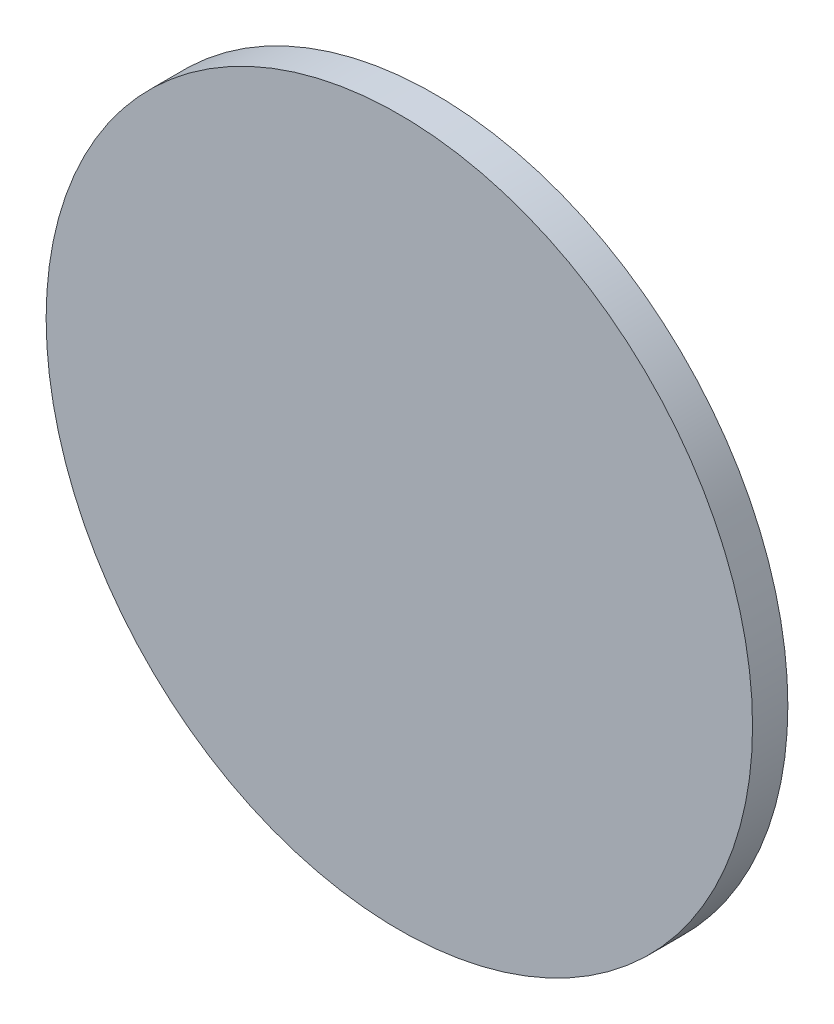
SolidWorks part; units mm, degrees
ref_plane "Front Plane" through (0, 0, 0) normal (0, 0, 1) x (1, 0, 0)
ref_plane "Top Plane" through (0, 0, 0) normal (0, 1, 0) x (1, 0, 0)
ref_plane "Right Plane" through (0, 0, 0) normal (1, 0, 0) x (0, 0, -1)
sketch "Sketch1" plane through (0, 0, 0) normal (0, 0, 1) x (1, 0, 0)
  circle A0 centre (0, 0) radius 50
  dimension "D1" = 100
extrude "Boss-Extrude1" add sketch "Sketch1" along normal blind 5
sketch "Sketch2" plane through (0, 0, 0) normal (0, 0, -1) x (-1, 0, 0)
  line L1 (-17, -35) -> (17, -35)
  line L2 (-17, -35) -> (-17, 35)
  line L3 (-17, 35) -> (17, 35)
  line L4 (17, -35) -> (17, 35)
  line L5 (-17, -35) -> (17, 35) construction
  line L6 (-17, 35) -> (17, -35) construction
  point P0 (0, 0)
  dimension "D1" = 70
  dimension "D2" = 34
extrude "Boss-Extrude3" add sketch "Sketch2" along normal blind 8
sketch "Sketch3" plane through (0, 0, -8) normal (0, 0, -1) x (-1, 0, 0)
  line L1 (-13.5, -31.5) -> (13.5, -31.5)
  line L2 (-13.5, -31.5) -> (-13.5, 31.5)
  line L3 (-13.5, 31.5) -> (13.5, 31.5)
  line L4 (13.5, -31.5) -> (13.5, 31.5)
  line L5 (-13.5, -31.5) -> (13.5, 31.5) construction
  line L6 (-13.5, 31.5) -> (13.5, -31.5) construction
  point P0 (0, 0)
  dimension "D1" = 63
  dimension "D2" = 27
extrude "Cut-Extrude1" cut sketch "Sketch3" against normal blind 8
sketch "Sketch4" plane through (0, -35, 0) normal (0, -1, 0) x (1, 0, 0)
  line L0 (-17, -8) -> (-17, 0) construction
  line L1 (-12, -2) -> (-8, -2)
  line L2 (-12, -2) -> (-12, -6)
  line L3 (-12, -6) -> (-8, -6)
  line L4 (-8, -2) -> (-8, -6)
  line L5 (17, 0) -> (-17, 0) construction
  dimension "D1" = 4
  dimension "D2" = 5
  dimension "D3" = 4
  dimension "D4" = 2
extrude "Cut-Extrude2" cut sketch "Sketch4" against normal through all
pattern_linear "LPattern1" count 3 spacing 10 along (1, 0, 0) of "Cut-Extrude2"
sketch "Sketch5" plane through (-17, 0, 0) normal (-1, 0, 0) x (0, 0, 1)
  line L0 (0, -35) -> (0, 35) construction
  line L1 (-6, 30) -> (-2, 30)
  line L2 (-6, 30) -> (-6, 26)
  line L3 (-6, 26) -> (-2, 26)
  line L4 (-2, 30) -> (-2, 26)
  line L5 (-8, 35) -> (0, 35) construction
  dimension "D1" = 4
  dimension "D2" = 4
  dimension "D3" = 2
  dimension "D4" = 5
extrude "Cut-Extrude3" cut sketch "Sketch5" against normal through all
pattern_linear "LPattern2" count 8 spacing 8 along (0, -1, 0) of "Cut-Extrude3"
sketch "Sketch6" plane through (0, 0, -8) normal (0, 0, -1) x (-1, 0, 0)
  line L1 (-13.5, 31.5) -> (13.5, 31.5)
  line L2 (-13.5, 31.5) -> (-13.5, -31.5)
  line L3 (-13.5, -31.5) -> (13.5, -31.5)
  line L4 (13.5, 31.5) -> (13.5, -31.5)
extrude "Boss-Extrude4" add sketch "Sketch6" against normal blind 8
sketch "Sketch7" plane through (0, 0, -8) normal (0, 0, -1) x (-1, 0, 0)
  line L1 (-12.8, -30.15) -> (12.8, -30.15)
  line L2 (-12.8, -30.15) -> (-12.8, 30.15)
  line L3 (-12.8, 30.15) -> (12.8, 30.15)
  line L4 (12.8, -30.15) -> (12.8, 30.15)
  line L5 (-12.8, -30.15) -> (12.8, 30.15) construction
  line L6 (-12.8, 30.15) -> (12.8, -30.15) construction
  point P0 (0, 0)
  dimension "D1" = 25.6
  dimension "D2" = 60.3
extrude "Cut-Extrude4" cut sketch "Sketch7" against normal blind 8
sketch "Sketch8" plane through (-17, 0, 0) normal (-1, 0, 0) x (0, 0, 1)
  line L1 (-6, -30) -> (-2, -30)
  line L2 (-6, -30) -> (-6, -26)
  line L3 (-6, -26) -> (-2, -26)
  line L4 (-2, -30) -> (-2, -26)
extrude "Cut-Extrude5" cut sketch "Sketch8" against normal through all
pattern_linear "LPattern4" count 2 spacing 0.1 along (0, 1, 0) of "LPattern2"
sketch "Sketch9" plane through (0, -35, 0) normal (0, -1, 0) x (1, 0, 0)
  line L1 (8, -2) -> (12, -2)
  line L2 (8, -2) -> (8, -6)
  line L3 (8, -6) -> (12, -6)
  line L4 (12, -2) -> (12, -6)
extrude "Cut-Extrude6" cut sketch "Sketch9" against normal through all
pattern_linear "LPattern5" count 2 spacing 0.1 along (-1, 0, 0) of "Cut-Extrude6", "LPattern1"
